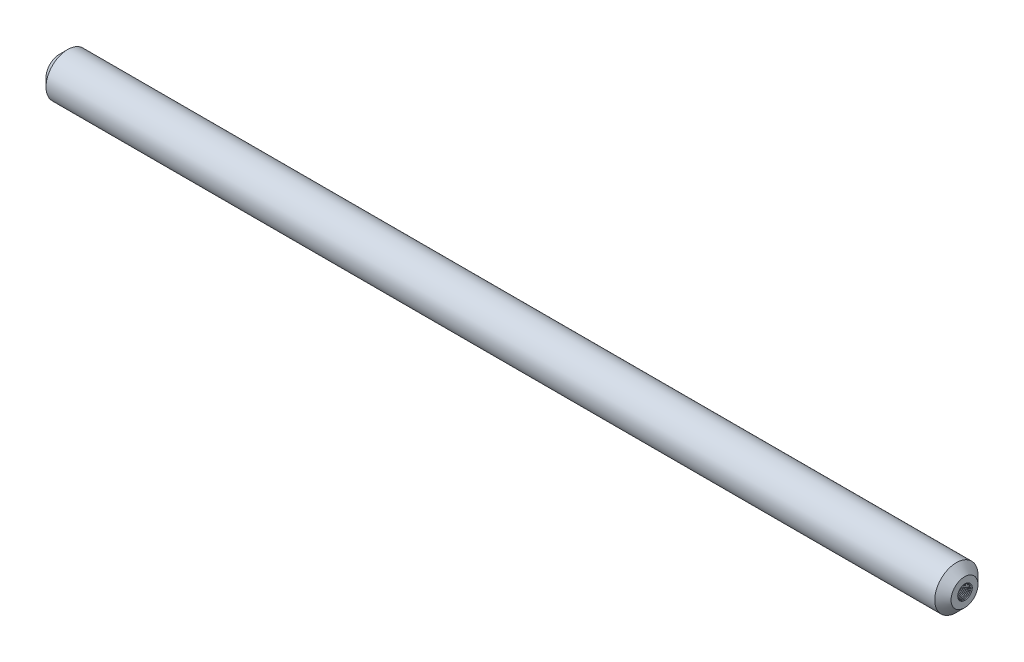
SolidWorks part; units mm, degrees
ref_plane "Front Plane" through (0, 0, 0) normal (0, 0, 1) x (1, 0, 0)
ref_plane "Top Plane" through (0, 0, 0) normal (0, 1, 0) x (1, 0, 0)
ref_plane "Right Plane" through (0, 0, 0) normal (1, 0, 0) x (0, 0, -1)
sketch "Sketch1" plane through (0, 0, 0) normal (1, 0, 0) x (0, 0, -1)
  circle A0 centre (0, 0) radius 7.9375
  dimension "D1" = 15.875
extrude "Boss-Extrude1" add sketch "Sketch1" against normal blind 332
sketch "Sketch2" plane through (0, 0, 0) normal (1, 0, 0) x (0, 0, -1)
  circle A0 centre (0, 0) radius 2.5
  dimension "D1" = 5
extrude "Cut-Extrude1" cut sketch "Sketch2" against normal blind 24
sketch "Sketch3" plane through (-332, 0, 0) normal (-1, 0, 0) x (0, 0, 1)
  circle A0 centre (0, 0) radius 2.5
  dimension "D1" = 5
extrude "Cut-Extrude2" cut sketch "Sketch3" against normal blind 24
sketch "Sketch4" plane through (0, 0, 0) normal (1, 0, 0) x (0, 0, -1)
  circle A0 centre (0, 0) radius 2.5
  dimension "D1" = 5
curve "Helix/Spiral1" pitch 0.5 height 18 turns 36
sketch "Sketch5" plane through (0, 0, 0) normal (1, 0, 0) x (0, 0, -1)
  line L1 (2.5, 0) -> (0, 0) construction
  circle A0 centre (0, 0) radius 2.5 construction
sketch3d "3DSketch5"
  point P0 (0, 0, -2.5)
sketch3d "3DSketch6"
  line L0 (0.2, 0, -2.5) -> (-0.2, 0, -2.5)
  line L2 (0.2, 0, -2.5) -> (-0.0014, 0, -2.8472)
  line L3 (-0.0014, 0, -2.8472) -> (-0.2, 0, -2.5)
  point P11 (0, 0, -2.5)
  dimension "D1" = 0.4
  dimension "D2" = 0.4
sweep "Cut-Sweep5" cut profiles "3DSketch6" path "Helix/Spiral1" align with end faces yes
sketch "Sketch8" plane through (-332, 0, 0) normal (-1, 0, 0) x (0, 0, 1)
  circle A0 centre (0, 0) radius 2.5
curve "Helix/Spiral3" pitch 0.5 height 18 turns 36
sketch "Sketch9" plane through (-332, 0, 0) normal (-1, 0, 0) x (0, 0, 1)
  line L0 (0, 0) -> (2.5, 0) construction
  circle A0 centre (0, 0) radius 2.5 construction
sketch3d "3DSketch7"
  point P0 (-332, 0, 2.5)
sketch3d "3DSketch8"
  line L0 (-331.8, 0, 2.5) -> (-332, 0, 2.8464)
  line L1 (-332.2, 0, 2.5) -> (-331.8, 0, 2.5)
  line L4 (-332, 0, 2.8464) -> (-332.2, 0, 2.5)
  point P6 (-332, 0, 2.5)
  point P7 (-332, 0, 2.5)
  dimension "D1" = 0.4
  dimension "D2" = 0.4
  dimension "D3" = 0.4
sweep "Cut-Sweep6" cut profiles "3DSketch8" path "Helix/Spiral3" align with end faces yes
chamfer "Chamfer1" distance 3 angle 45 2 edges at (-332, 0, -7.9375) (0, 0, -7.9375)
